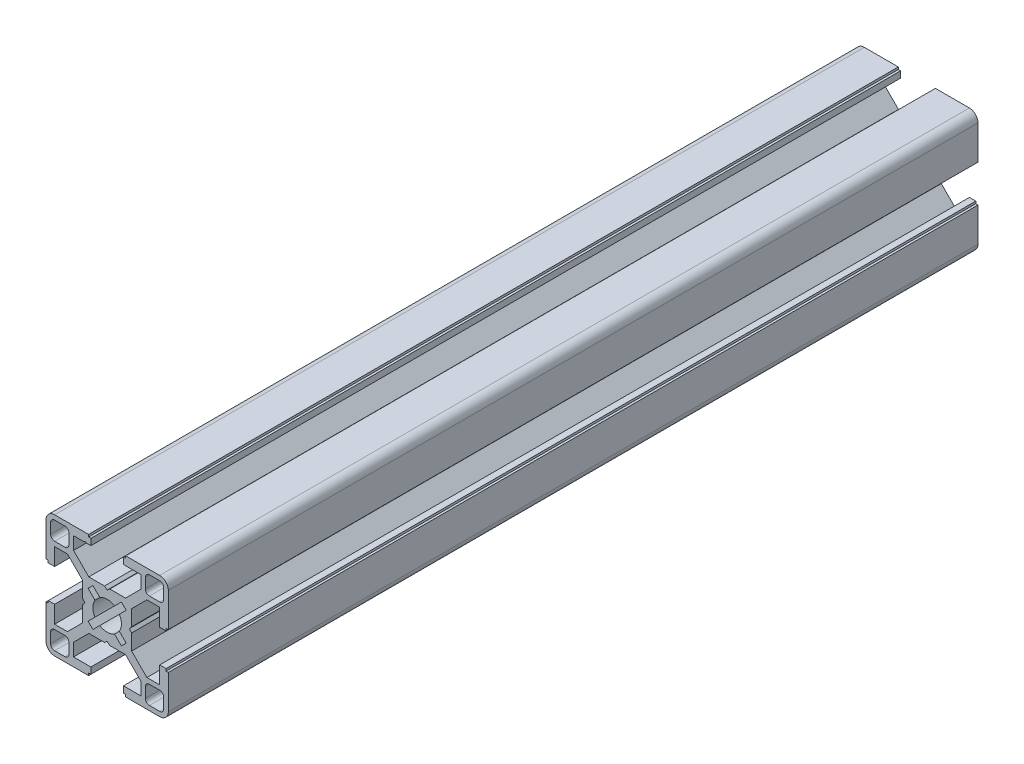
SolidWorks part; units mm, degrees
material "6061-T6 (SS)"
ref_plane "Front Plane" through (0, 0, 0) normal (0, 0, 1) x (1, 0, 0)
ref_plane "Top Plane" through (0, 0, 0) normal (0, 1, 0) x (1, 0, 0)
ref_plane "Right Plane" through (0, 0, 0) normal (1, 0, 0) x (0, 0, -1)
sketch "Sketch2" plane through (0, 0, 0) normal (0, 0, 1) x (1, 0, 0)
  line L0 (0, 15) -> (0, -15) construction
  line L1 (-15, 0) -> (15, 0) construction
  line L2 (4, -15) -> (15, -15)
  line L3 (15, -15) -> (15, -4)
  line L4 (4, -15) -> (4, -12.885)
  line L6 (8.25, -9.7455) -> (4.5045, -6)
  line L7 (0, 0) -> (15, -15) construction
  line L8 (15, -4) -> (12.885, -4)
  line L11 (4.55, -15) -> (4.55, -14.45) construction
  line L12 (4, -12.885) -> (8.25, -12.885)
  line L13 (8.25, -12.885) -> (8.25, -9.7455)
  line L14 (4.55, -14.45) -> (4, -14.45) construction
  line L15 (14.45, -4) -> (14.45, -4.55) construction
  line L16 (14.45, -4.55) -> (15, -4.55) construction
  line L17 (12.885, -4) -> (12.885, -8.25)
  line L18 (12.885, -8.25) -> (9.7455, -8.25)
  line L19 (9.7455, -8.25) -> (6, -4.5045)
  line L20 (7.8728, -6.3772) -> (6.3772, -7.8728) construction
  line L21 (11.625, -13.875) -> (11.625, -15) construction
  line L22 (9.375, -13.875) -> (13.875, -13.875)
  line L23 (9.375, -13.875) -> (9.375, -9.375)
  line L24 (9.375, -9.375) -> (13.875, -9.375)
  line L25 (13.875, -13.875) -> (13.875, -9.375)
  line L26 (11.625, -9.375) -> (11.625, -13.875) construction
  line L27 (9.375, -11.625) -> (13.875, -11.625) construction
  line L28 (13.875, -11.625) -> (15, -11.625) construction
  line L29 (8.25, -12.885) -> (9.375, -12.885) construction
  line L30 (4.5045, -6) -> (0.6555, -6)
  line L31 (0.6555, -6) -> (0, -5.45)
  line L32 (0, -6) -> (0, -5.45) construction
  circle A0 centre (0, 0) radius 3.5
  arc A2 (9.375, -12.885) -> (10.365, -13.875) centre (10.365, -12.885) ccw construction
  point P8 (0, -6)
  point P15 (4.55, -15)
  point P16 (7.125, -7.125)
  point P33 (11.625, -11.625)
  dimension "Center Hole Diameter" = 7
  dimension "Rail Height" = 30
  dimension "Rail Width" = 30
  dimension "T-Slot Width" = 8
  dimension "Slot Depth" = 9
  dimension "Slot Inner Width" = 16.5
  dimension "Step Width" = 9.1
  dimension "D1" = 1.125
  dimension "D2" = 2.115
  dimension "D3" = 50
sketch "Sketch3" plane through (0, 0, 0) normal (1, 0, 0) x (0, 0, -1)
  line L0 (-76.2, -15) -> (76.2, -15) construction
  line L1 (-50.8, 0) -> (50.8, 0) construction
  dimension "D1" = 25.4
  dimension "Length" = 152.4
sketch "Sketch4" plane through (0, 0, 0) normal (0, 0, 1) x (1, 0, 0)
  line L22 (0, -5.45) -> (0.6555, -6)
  line L23 (0.6555, -6) -> (4.5045, -6)
  line L24 (4.5045, -6) -> (8.25, -9.7455)
  line L25 (8.25, -9.7455) -> (8.25, -12.885)
  line L26 (8.25, -12.885) -> (4, -12.885)
  line L27 (4, -12.885) -> (4, -14.45)
  line L28 (4, -14.45) -> (4.55, -14.45)
  line L29 (4.55, -14.45) -> (4.55, -15)
  line L30 (4.55, -15) -> (12.885, -15)
  line L31 (4, -15) -> (15, -15) construction
  line L32 (15, -15) -> (15, -4) construction
  line L33 (15, -12.885) -> (15, -4.55)
  line L34 (15, -4.55) -> (14.45, -4.55)
  line L35 (14.45, -4.55) -> (14.45, -4)
  line L36 (14.45, -4) -> (12.885, -4)
  line L37 (12.885, -4) -> (12.885, -8.25)
  line L38 (12.885, -8.25) -> (9.7455, -8.25)
  line L39 (9.7455, -8.25) -> (6, -4.5045)
  line L40 (6, -4.5045) -> (6, -0.6555)
  line L41 (6, -0.6555) -> (5.45, 0)
  line L42 (-15, 0) -> (15, 0) construction
  line L43 (0, -5.45) -> (0, -3.5)
  line L44 (0, 15) -> (0, -15) construction
  line L45 (3.5, 0) -> (5.45, 0)
  line L46 (1.8108, -2.9952) -> (3.4913, -4.6757)
  line L47 (3.4913, -4.6757) -> (4.6757, -3.4913)
  line L48 (4.6757, -3.4913) -> (2.9952, -1.8108)
  line L49 (0, 0) -> (15, -15) construction
  line L50 (9.375, -13.875) -> (13.875, -13.875) construction
  line L51 (13.875, -13.875) -> (13.875, -9.375) construction
  line L52 (9.375, -13.875) -> (9.375, -9.375) construction
  line L53 (9.375, -9.375) -> (13.875, -9.375) construction
  line L54 (9.375, -10.365) -> (9.375, -12.885)
  line L55 (10.365, -13.875) -> (12.885, -13.875)
  line L56 (13.875, -12.885) -> (13.875, -10.365)
  line L57 (10.365, -9.375) -> (12.885, -9.375)
  arc A12 (12.885, -15) -> (15, -12.885) centre (12.885, -12.885) ccw
  circle A13 centre (0, 0) radius 3.5 construction
  arc A14 (0, -3.5) -> (1.8108, -2.9952) centre (0, 0) ccw
  arc A15 (3.5, 0) -> (2.9952, -1.8108) centre (0, 0) cw
  circle A16 centre (0, 0) radius 5.775 construction
  arc A17 (9.375, -12.885) -> (10.365, -13.875) centre (10.365, -12.885) ccw
  arc A18 (9.375, -12.885) -> (10.365, -13.875) centre (10.365, -12.885) ccw construction
  arc A19 (12.885, -13.875) -> (13.875, -12.885) centre (12.885, -12.885) ccw
  arc A20 (9.375, -10.365) -> (10.365, -9.375) centre (10.365, -10.365) cw
  arc A21 (12.885, -9.375) -> (13.875, -10.365) centre (12.885, -10.365) cw
  point P40 (4.0835, -4.0835)
  dimension "D1" = 11.55
  dimension "D2" = 0.22
extrude "Boss-Extrude1" add sketch "Sketch4" along normal blind 198.6
mirror "Mirror1" about plane through (0, 0, 0) normal (1, 0, 0) of bodies 134
mirror "Mirror2" about plane through (0, 0, 0) normal (0, 1, 0) of bodies 135
sketch "Sketch5" plane through (0, 0, 198.6) normal (0, 0, 1) x (1, 0, 0)
  line L0 (-5.675, 12.885) -> (-5.4, 13.16)
  line L1 (-8.25, 12.885) -> (-4, 12.885) construction
  line L2 (-5.4, 13.16) -> (-5.125, 12.885)
  line L3 (0, 15) -> (0, -15) construction
  line L4 (-5.675, 12.885) -> (-5.125, 12.885)
  dimension "D1" = 0.275
  dimension "D2" = 5.4
extrude "Cut-Extrude1" cut sketch "Sketch5" against normal through all both and the other way through all
equation "\"D1@Boss-Extrude1\"= \"azimuth_mounting_hole_distance\" - 30mm"
equation "\"D1@Sketch2\"=\"Slot Depth@Sketch2\"*0.125"
equation "\"D2@Sketch2\"=\"Slot Depth@Sketch2\"*0.235"
equation "\"D1@Sketch4\"=\"Center Hole Diameter@Sketch2\"*1.65"
equation "\"D2@Sketch4\"=(\"Step Width@Sketch2\"-\"T-Slot Width@Sketch2\")*0.2"
equation "\"D1@Sketch5\"=(\"Step Width@Sketch2\"-\"T-Slot Width@Sketch2\")*0.5*0.5"
equation "\"D2@Sketch5\"=\"T-Slot Width@Sketch2\"*1.35*0.5"
equation "\"altitude_horizontal_rail_length\"=10in"
equation "\"altitude_vertictal_rail_length\"=12in"
equation "\"table_length\"=72in"
equation "\"table_width\"=25in"
equation "\"table_thickness\"=1.75in"
equation "\"azimuth_horizontal_rail_length\"=(\"altitude_horizontal_rail_length\"+6in-0.29in)"
equation "\"azimuth_vertictal_rail_length_short\"=(\"altitude_vertictal_rail_length\"-5in)"
equation "\"azimuth_vertictal_rail_length_long\"=(\"azimuth_vertictal_rail_length_short\"+4in)"
equation "\"azimuth_mounting_hole_distance\"=9in"
